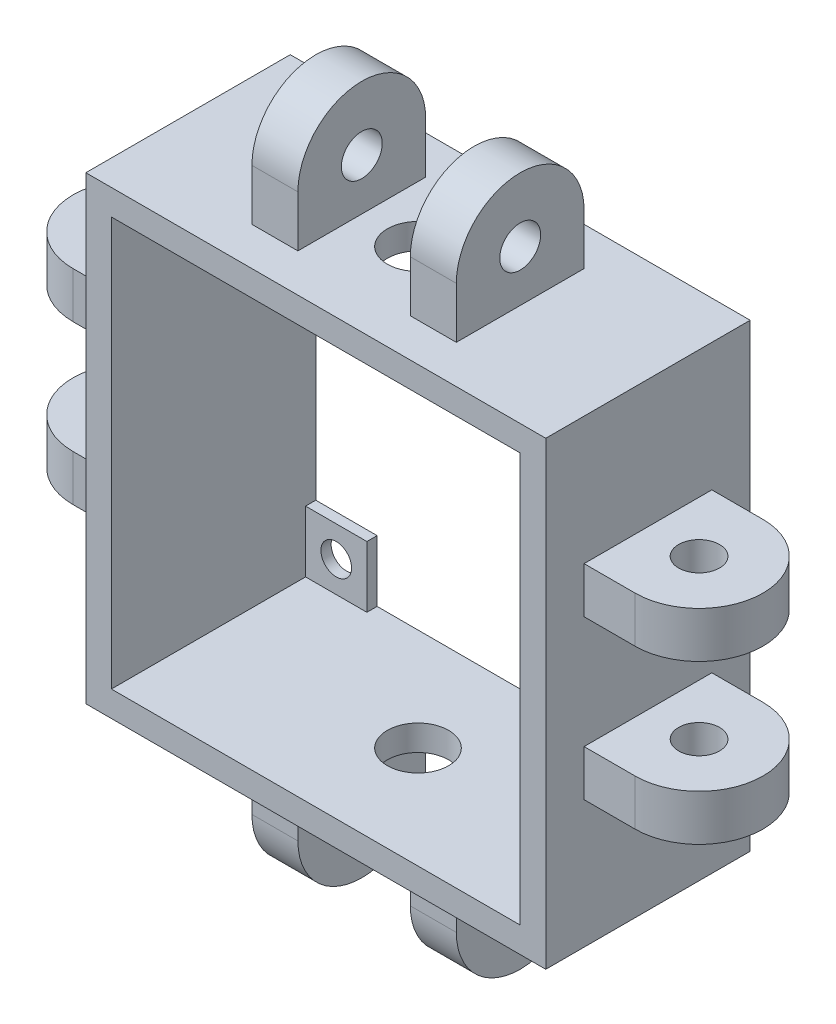
SolidWorks part; units mm, degrees
material "2024 合金"
ref_plane "前视基准面" through (0, 0, 0) normal (0, 0, 1) x (1, 0, 0)
ref_plane "上视基准面" through (0, 0, 0) normal (0, 1, 0) x (1, 0, 0)
ref_plane "右视基准面" through (0, 0, 0) normal (1, 0, 0) x (0, 0, -1)
sketch "草图1" plane through (0, 0, 0) normal (0, 0, 1) x (1, 0, 0)
  line L1 (-45, -45) -> (45, -45)
  line L2 (-45, -45) -> (-45, 45)
  line L3 (-45, 45) -> (45, 45)
  line L4 (45, -45) -> (45, 45)
  line L5 (-45, -45) -> (45, 45) construction
  line L6 (-45, 45) -> (45, -45) construction
  line L7 (-40, -40) -> (40, -40)
  line L8 (-40, -40) -> (-40, 40)
  line L9 (-40, 40) -> (40, 40)
  line L10 (40, -40) -> (40, 40)
  line L11 (-40, -40) -> (40, 40) construction
  line L12 (-40, 40) -> (40, -40) construction
  point P0 (0, 0)
  point P7 (0, 0)
  dimension "D1" = 90
  dimension "D2" = 90
  dimension "D3" = 80
  dimension "D4" = 80
extrude "凸台-拉伸1" add sketch "草图1" along normal blind 40
sketch "草图3" plane through (0, 45, 0) normal (0, 1, 0) x (1, 0, 0)
  line L0 (0, 0) -> (0, -20) construction
  line L1 (45, 0) -> (-45, 0) construction
  circle A0 centre (0, -20) radius 6
  dimension "D2" = 12
  dimension "D1" = 20
extrude "切除-拉伸2" cut sketch "草图3" against normal through all
sketch "草图4" plane through (0, -1.9977, 74.2652) normal (1, 0, 0) x (0, 0, -1)
  line L0 (41.7652, -43.0023) -> (41.7652, -53.0023)
  line L1 (66.7652, -53.0023) -> (66.7652, -43.0023)
  line L2 (66.7652, -43.0023) -> (41.7652, -43.0023)
  line L3 (54.2652, -42.5) -> (54.2652, -53.0023) construction
  line L4 (34.2652, -43.0023) -> (74.2652, -43.0023) construction
  arc A0 (41.7652, -53.0023) -> (66.7652, -53.0023) centre (54.2652, -53.0023) ccw
  circle A1 centre (54.2652, -53.0023) radius 4
  dimension "D3" = 8
  dimension "D1" = 25
  dimension "D2" = 10
extrude "凸台-拉伸2" add sketch "草图4" along normal blind 20 and the other way blind 20
sketch "草图5" plane through (0, 0, 7.5) normal (0, 0, -1) x (-1, 0, 0)
  line L0 (0, 0) -> (0, -60) construction
  line L1 (11, -45) -> (-11, -45)
  line L2 (11, -45) -> (11, -75)
  line L3 (11, -75) -> (-11, -75)
  line L4 (-11, -45) -> (-11, -75)
  line L5 (11, -45) -> (-11, -75) construction
  line L6 (11, -75) -> (-11, -45) construction
  line L7 (45, -45) -> (-45, -45) construction
  point P0 (0, -60)
  dimension "D1" = 22
  dimension "D2" = 30
extrude "切除-拉伸3" cut sketch "草图5" against normal through all
ref_plane "基准面1" through (0, 0, 0) normal (0, -1, 0) x (-1, 0, 0)
ref_plane "基准面2" through (0, 0, 0) normal (1, 0, 0) x (0, 0, -1)
ref_axis "基准轴1" through (0, 0, 42) along (0, 0, -1)
pattern_circular "阵列(圆周)3" count 4 over 360 about axis through (0, 0, 42) along (0, 0, -1) of "切除-拉伸3", "凸台-拉伸2"
sketch "草图6" plane through (0, 0, 0) normal (0, 0, -1) x (-1, 0, 0)
  line L0 (0, 0) -> (0, -50.3138) construction
  line L1 (-40, -40) -> (-28, -40)
  line L2 (-40, -40) -> (-40, -28)
  line L3 (-40, -28) -> (-28, -28)
  line L4 (-28, -40) -> (-28, -28)
  line L5 (28, -40) -> (28, -28)
  line L6 (40, -28) -> (28, -28)
  line L7 (40, -40) -> (40, -28)
  line L8 (40, -40) -> (28, -40)
  line L9 (0, 0) -> (51.5178, 0) construction
  line L10 (-28, 40) -> (-28, 28)
  line L11 (-40, 28) -> (-28, 28)
  line L12 (-40, 40) -> (-40, 28)
  line L13 (-40, 40) -> (-28, 40)
  line L14 (40, 40) -> (28, 40)
  line L15 (40, 40) -> (40, 28)
  line L16 (40, 28) -> (28, 28)
  line L17 (28, 40) -> (28, 28)
  dimension "D1" = 12
  dimension "D2" = 12
extrude "凸台-拉伸3" add sketch "草图6" against normal blind 2
sketch "草图7" plane through (0, 0, 0) normal (0, 0, -1) x (-1, 0, 0)
  line L0 (-40, 28) -> (-28, 28) construction
  line L1 (-28, 28) -> (-28, 40) construction
  line L2 (28, 28) -> (40, 28) construction
  line L3 (28, 40) -> (28, 28) construction
  line L4 (40, -28) -> (28, -28) construction
  line L5 (28, -28) -> (28, -40) construction
  line L6 (-28, -28) -> (-40, -28) construction
  line L7 (-28, -40) -> (-28, -28) construction
  circle A0 centre (-34, 34) radius 3
  circle A1 centre (34, 34) radius 3
  circle A2 centre (34, -34) radius 3
  circle A3 centre (-34, -34) radius 3
  dimension "D3" = 6
  dimension "D6" = 6
  dimension "D9" = 6
  dimension "D12" = 6
  dimension "D1" = 6
  dimension "D2" = 6
  dimension "D4" = 6
  dimension "D5" = 6
  dimension "D7" = 6
  dimension "D8" = 6
  dimension "D10" = 6
  dimension "D11" = 6
extrude "切除-拉伸4" cut sketch "草图7" against normal up to next
